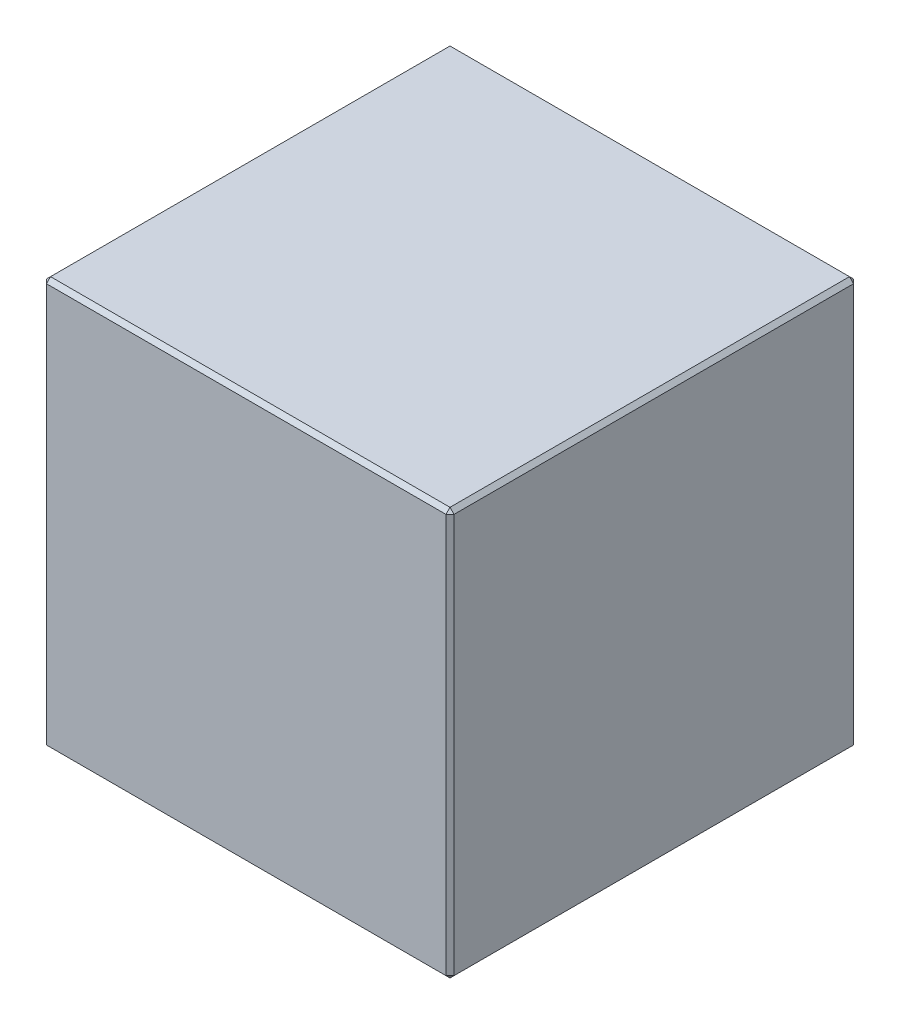
SolidWorks part; units mm, degrees
ref_plane "Front" through (0, 0, 0) normal (0, 0, 1) x (1, 0, 0)
ref_plane "Top" through (0, 0, 0) normal (0, 1, 0) x (1, 0, 0)
ref_plane "Right" through (0, 0, 0) normal (1, 0, 0) x (0, 0, -1)
ref_axis "Z AXIS" through (0, 0, 10.1914) along (0, 0, -1)
ref_axis "Y AXIS" through (0, 16.6631, 0) along (0, -1, 0)
ref_axis "X AXIS" through (18.31, 0, 0) along (-1, 0, 0)
sketch "Sketch1" plane through (0, 0, 0) normal (0, 1, 0) x (1, 0, 0)
  line L1 (0, 0) -> (60, 0)
  line L2 (0, 0) -> (0, 60)
  line L3 (0, 60) -> (60, 60)
  line L4 (60, 0) -> (60, 60)
  dimension "D1" = 60
extrude "Boss-Extrude1" add sketch "Sketch1" along normal blind 60
chamfer "Chamfer1" distance 0.6 angle 45 12 edges at (60, 0, -30) (0, 0, -30) (60, 60, -30) (60, 30, -60) (30, 60, -60) (30, 0, -60) (0, 30, -60) (0, 60, -30) (0, 30, 0) (30, 60, 0) (60, 30, 0) (30, 0, 0)
